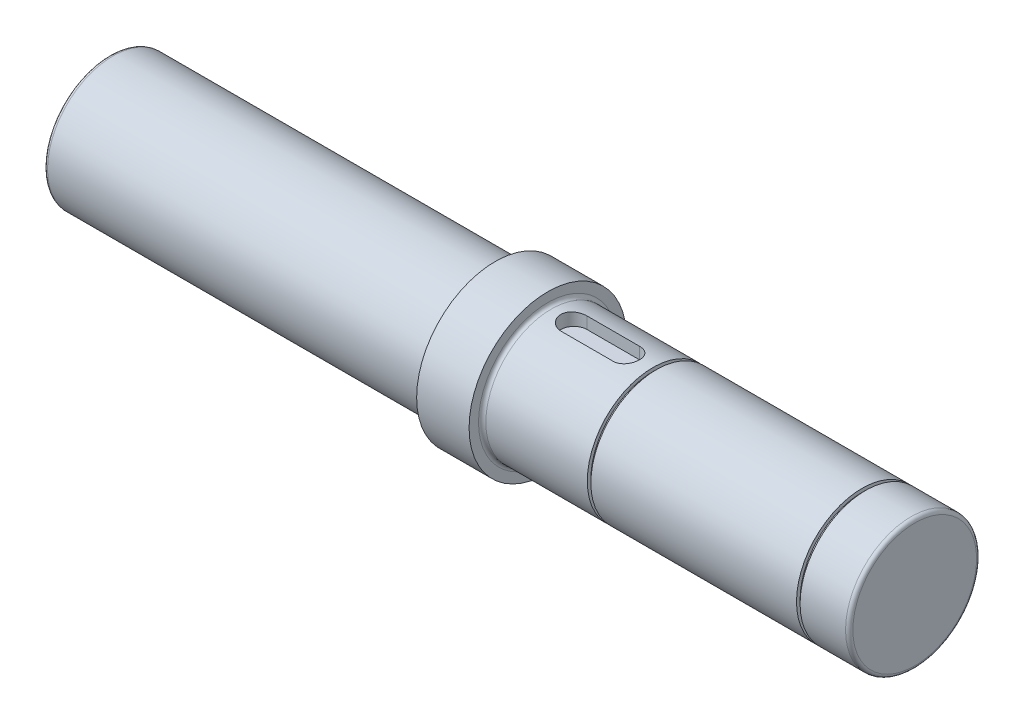
SolidWorks part; units mm, degrees
ref_plane "Front Plane" through (0, 0, 0) normal (0, 0, 1) x (1, 0, 0)
ref_plane "Top Plane" through (0, 0, 0) normal (0, 1, 0) x (1, 0, 0)
ref_plane "Right Plane" through (0, 0, 0) normal (1, 0, 0) x (0, 0, -1)
sketch "Sketch1" plane through (0, 0, 0) normal (0, 1, 0) x (1, 0, 0)
  line L0 (38.1, 0) -> (63.5, 0) construction
  line L1 (0, 0) -> (-186.944, 0)
  line L2 (0, 0) -> (0, 31.75)
  line L3 (-1.778, 31.75) -> (-185.166, 31.75)
  line L4 (-186.944, 0) -> (-186.944, 29.972)
  line L5 (0, 0) -> (203.2, 0)
  line L6 (0, 0) -> (0, 31.75)
  line L7 (27.178, 31.75) -> (201.422, 31.75)
  line L8 (203.2, 0) -> (203.2, 29.972)
  line L9 (25.4, 31.75) -> (76.2, 31.75)
  line L10 (25.4, 31.75) -> (25.4, 0)
  line L11 (25.4, 0) -> (76.2, 0)
  line L12 (76.2, 31.75) -> (76.2, 0)
  line L13 (25.4, 31.75) -> (76.2, 0) construction
  line L14 (25.4, 0) -> (76.2, 31.75) construction
  line L15 (25.4, 0) -> (0, 0)
  line L16 (25.4, 33.528) -> (25.4, 38.1)
  line L17 (25.4, 38.1) -> (0, 38.1)
  line L18 (0, 33.528) -> (0, 38.1)
  line L19 (76.327, 31.75) -> (78.0542, 31.75)
  line L20 (76.327, 31.75) -> (76.327, 30.0228)
  line L21 (76.327, 30.0228) -> (78.0542, 30.0228)
  line L22 (78.0542, 31.75) -> (78.0542, 30.0228)
  line L23 (76.327, 31.75) -> (78.0542, 30.0228) construction
  line L24 (76.327, 30.0228) -> (78.0542, 31.75) construction
  line L25 (177.673, 31.75) -> (179.4002, 31.75)
  line L26 (177.673, 31.75) -> (177.673, 30.0228)
  line L27 (177.673, 30.0228) -> (179.4002, 30.0228)
  line L28 (179.4002, 31.75) -> (179.4002, 30.0228)
  line L29 (177.673, 31.75) -> (179.4002, 30.0228) construction
  line L30 (177.673, 30.0228) -> (179.4002, 31.75) construction
  line L31 (38.1, 6.35) -> (63.5, 6.35)
  line L32 (38.1, -6.35) -> (63.5, -6.35)
  line L33 (50.8, 0) -> (50.8, 15.875) construction
  arc A0 (-186.944, 29.972) -> (-185.166, 31.75) centre (-185.166, 29.972) cw
  arc A1 (203.2, 29.972) -> (201.422, 31.75) centre (201.422, 29.972) ccw
  arc A2 (27.178, 31.75) -> (25.4, 33.528) centre (27.178, 33.528) cw
  arc A3 (-1.778, 31.75) -> (0, 33.528) centre (-1.778, 33.528) ccw
  arc A4 (38.1, 6.35) -> (38.1, -6.35) centre (38.1, 0) ccw
  arc A5 (63.5, -6.35) -> (63.5, 6.35) centre (63.5, 0) ccw
  point P12 (50.8, 15.875)
  point P24 (77.1906, 30.8864)
  point P25 (178.5366, 30.8864)
  point P37 (50.8, 0)
  dimension "D12" = 1.778
  dimension "D13" = 25.4
  dimension "D1" = 186.944
  dimension "D2" = 31.75
  dimension "D3" = 203.2
  dimension "D4" = 25.4
  dimension "D5" = 50.8
  dimension "D6" = 38.1
  dimension "D7" = 0.127
  dimension "D8" = 1.7272
  dimension "D9" = 1.7272
  dimension "D10" = 25.527
  dimension "D11" = 1.7272
  dimension "D14" = 12.7
revolve "Revolve1" add sketch "Sketch1" angle 360 about L5 region at (-78.5595, 0, -16.3217) region at (50.8, 0, -17.9518) region at (50.8, 0, -3.0397) region at (139.7069, 0, -15.8501)
extrude "Cut-Extrude1" cut sketch "Sketch1<4>" along normal through all from offset 25.4 contours L32 A5 L31 A4
sketch "Sketch1<4>" plane through (0, 0, 0) normal (0, 1, 0) x (1, 0, 0) same geometry as "Sketch1"
